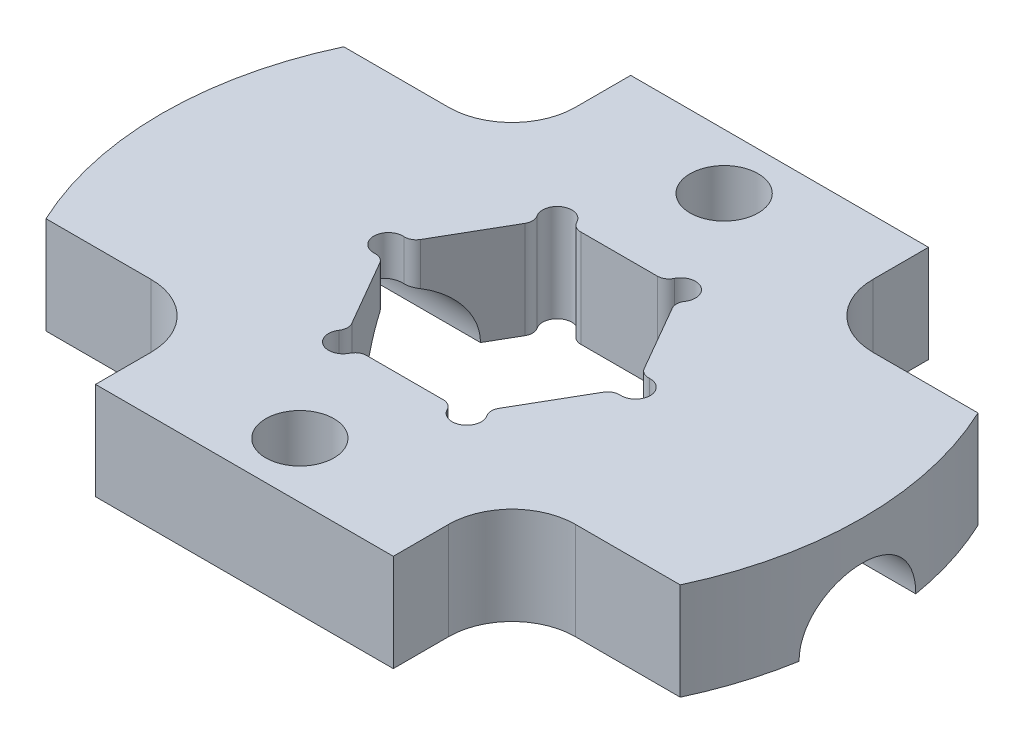
SolidWorks part; units mm, degrees
material "3.3547 (EN-AW 5083)"
ref_plane "Vorne" through (0, 0, 0) normal (0, 0, 1) x (1, 0, 0)
ref_plane "Oben" through (0, 0, 0) normal (0, 1, 0) x (1, 0, 0)
ref_plane "Rechts" through (0, 0, 0) normal (1, 0, 0) x (0, 0, -1)
sketch "Skizze1" plane through (0, 0, 0) normal (0, 1, 0) x (1, 0, 0)
  circle A0 centre (0, 0) radius 18
  dimension "D1" = 36
extrude "Aufsatz-Linear austragen1" add sketch "Skizze1" along normal blind 5
sketch "Skizze2" plane through (0, 5, 0) normal (0, 1, 0) x (1, 0, 0)
  line L1 (-18, -13.75) -> (18, -13.75)
  line L2 (-18, -13.75) -> (-18, 13.75)
  line L3 (-18, 13.75) -> (18, 13.75)
  line L4 (18, -13.75) -> (18, 13.75)
  line L5 (-18, -13.75) -> (18, 13.75) construction
  line L6 (-18, 13.75) -> (18, -13.75) construction
  circle A0 centre (0, 0) radius 18 construction
  point P0 (0, 0)
  dimension "D1" = 27.5
extrude "Schnitt-Linear austragen1" cut sketch "Skizze2" against normal through all and the other way through all flip side to cut
hole_wizard "Ø3.5 (3.5) Durchmesser Bohrung1" positions "Skizze3" profile "Skizze4" hole size "Ø3.5" standard "DIN" end condition through all
sketch "Skizze3" plane through (0, 5, 0) normal (0, 1, 0) x (1, 0, 0)
  line L0 (0, -2.75) -> (0, 2.75) construction
  line L1 (-2.75, 0) -> (2.75, 0) construction
  point P0 (0, 10.9)
  point P4 (0, -10.9)
  dimension "D1" = 10.9
  dimension "D2" = 21.8
sketch "Skizze4" plane through (0, 5, -10.9) normal (1, 0, 0) x (0, 0, 1)
  line L0 (0, 0) -> (0, 5)
  line L1 (0, 5) -> (1.75, 5)
  line L2 (1.75, 5) -> (1.75, 0)
  line L5 (1.75, 0) -> (0, 0)
  line L11 (0, -6.35) -> (0, 107.95) construction
  dimension "Bohrerdurchmesser" = 3.5
  dimension "Bohrungstiefe" = 5
sketch "Skizze5" plane through (0, 5, 0) normal (0, 1, 0) x (1, 0, 0)
  line L0 (-10.9, 7.65) -> (-17.8885, 7.65)
  line L1 (-7.65, 10.9) -> (-7.65, 14.15)
  line L2 (-7.65, 14.15) -> (-17.8885, 14.15)
  line L3 (-17.8885, 14.15) -> (-17.8885, 7.65)
  line L4 (0, -2.75) -> (0, 2.75) construction
  line L5 (-2.75, 0) -> (2.75, 0) construction
  line L6 (17.8885, 14.15) -> (17.8885, 7.65)
  line L7 (7.65, 14.15) -> (17.8885, 14.15)
  line L8 (7.65, 10.9) -> (7.65, 14.15)
  line L9 (10.9, 7.65) -> (17.8885, 7.65)
  line L10 (-17.8885, -14.15) -> (-17.8885, -7.65)
  line L11 (-7.65, -14.15) -> (-17.8885, -14.15)
  line L12 (-7.65, -10.9) -> (-7.65, -14.15)
  line L13 (-10.9, -7.65) -> (-17.8885, -7.65)
  line L14 (10.9, -7.65) -> (17.8885, -7.65)
  line L15 (7.65, -10.9) -> (7.65, -14.15)
  line L16 (7.65, -14.15) -> (17.8885, -14.15)
  line L17 (17.8885, -14.15) -> (17.8885, -7.65)
  arc A0 (-10.9, 7.65) -> (-7.65, 10.9) centre (-10.9, 10.9) ccw
  arc A4 (10.9, 7.65) -> (7.65, 10.9) centre (10.9, 10.9) cw
  arc A5 (-10.9, -7.65) -> (-7.65, -10.9) centre (-10.9, -10.9) cw
  arc A6 (10.9, -7.65) -> (7.65, -10.9) centre (10.9, -10.9) ccw
  dimension "D1" = 6.5
  dimension "D2" = 10.9
  dimension "D3" = 10.9
extrude "Schnitt-Linear austragen2" cut sketch "Skizze5" against normal through all
sketch "Skizze6" plane through (0, 5, 0) normal (0, 1, 0) x (1, 0, 0)
  line L0 (-2.75, 0) -> (2.75, 0) construction
  line L1 (6.3509, 0) -> (3.1754, 5.5)
  line L2 (3.1754, 5.5) -> (-3.1754, 5.5)
  line L3 (-3.1754, 5.5) -> (-6.3509, 0)
  line L4 (-6.3509, 0) -> (-3.1754, -5.5)
  line L5 (-3.1754, -5.5) -> (3.1754, -5.5)
  line L6 (3.1754, -5.5) -> (6.3509, 0)
  circle A0 centre (0, 0) radius 5.5 construction
  dimension "D1" = 11
extrude "Schnitt-Linear austragen3" cut sketch "Skizze6" against normal through all
sketch "Skizze7" plane through (0, 0, 0) normal (1, 0, 0) x (0, 0, -1)
  circle A0 centre (0, 0) radius 3
  dimension "D1" = 6
extrude "Schnitt-Linear austragen4" cut sketch "Skizze7" against normal mid plane 45
hole_wizard "Ø1.5 (1.5) Durchmesser Bohrung1" positions "Skizze8" profile "Skizze9" hole size "Ø1.5" standard "DIN" end condition through all
sketch "Skizze8" plane through (0, 5, 0) normal (0, 1, 0) x (1, 0, 0)
  point P0 (3.1754, 5.5)
  point P3 (-3.1754, 5.5)
  point P6 (-6.3509, 0)
  point P9 (-3.1754, -5.5)
  point P12 (3.1754, -5.5)
  point P15 (6.3509, 0)
sketch "Skizze9" plane through (3.1754, 5, -5.5) normal (1, 0, 0) x (0, 0, 1)
  line L0 (0, 0) -> (0, 5.1724)
  line L1 (0, 5.1724) -> (0.75, 5.1724)
  line L2 (0.75, 5.1724) -> (0.75, 0)
  line L5 (0.75, 0) -> (0, 0)
  line L11 (0, -6.35) -> (0, 107.95) construction
  dimension "Bohrerdurchmesser" = 1.5
  dimension "Bohrungstiefe" = 5.1724
fillet "Verrundung1" radius 0.6 12 edges at (-5.9759, 3.9644, -0.6495) (-5.9759, 3.9644, 0.6495) (-3.5504, 2.5, 4.8505) (-2.4254, 2.5, 5.5) (2.4254, 2.5, 5.5) (3.5504, 2.5, 4.8505) (5.9759, 3.9644, 0.6495) (5.9759, 3.9644, -0.6495) (3.5504, 2.5, -4.8505) (2.4254, 2.5, -5.5) (-2.4254, 2.5, -5.5) (-3.5504, 2.5, -4.8505)
